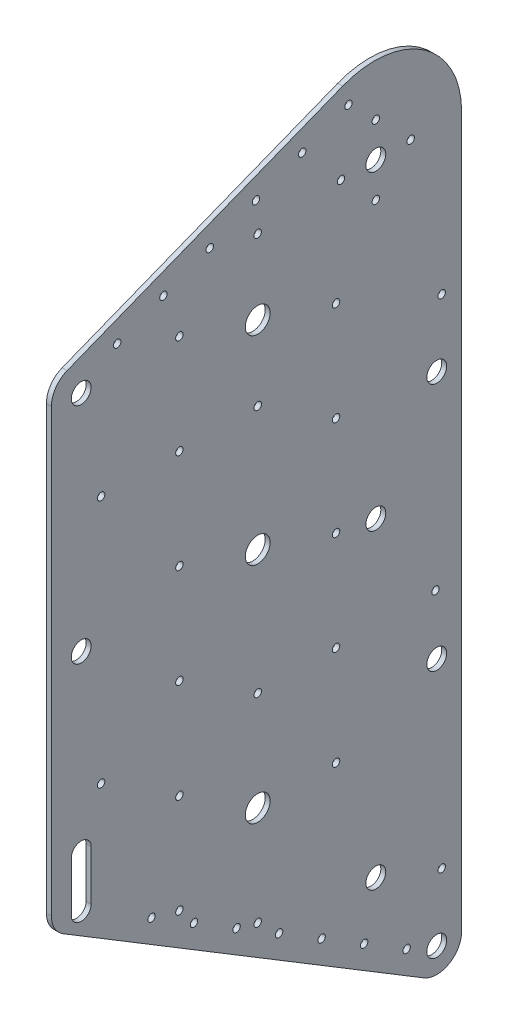
SolidWorks part; units mm, degrees
material "6061 Alloy"
ref_plane "Front Plane" through (0, 0, 0) normal (0, 0, 1) x (1, 0, 0)
ref_plane "Top Plane" through (0, 0, 0) normal (0, 1, 0) x (1, 0, 0)
ref_plane "Right Plane" through (0, 0, 0) normal (1, 0, 0) x (0, 0, -1)
sketch "Sketch2" plane through (0, 0, 0) normal (-1, 0, 0) x (0, 1, 0)
  line L0 (0, 0) -> (65, 165)
  line L1 (65, 165) -> (-290, 165)
  line L2 (-290, 165) -> (-190, 0)
  line L3 (-90.75, 0) -> (90.75, 0) construction
  line L4 (-190, 0) -> (0, 0)
  dimension "D1" = 355
  dimension "D2" = 190
  dimension "D3" = 165
  dimension "D4" = 65
extrude "Boss-Extrude1" add sketch "Sketch2" along normal blind 2
fillet "Fillet1" radius 10 3 edges at (-1, -190, 0) (-1, -290, -165) (-1, 0, 0)
sketch "Sketch3" plane through (-2, 0, 0) normal (-1, 0, 0) x (0, 1, 0)
  line L0 (-192.1703, 12) -> (-192.1703, 3.3924) construction
  line L1 (65, 165) -> (-272.2462, 165) construction
  line L2 (-280.7982, 149.817) -> (-192.9194, 4.817) construction
  line L3 (2.4955, 6.3348) -> (65, 165) construction
  line L4 (-164.1703, 12) -> (-164.1703, 3.3924) construction
  line L5 (-90.75, 0) -> (90.75, 0) construction
  line L6 (-261.9073, 134.0821) -> (-194.8085, 23.369) construction
  line L7 (-4.3733, 10.7251) -> (45.6685, 137.7543) construction
  line L8 (-102.1703, 12) -> (-102.1703, 4.9013) construction
  line L9 (-188.1703, 8) -> (-168.1703, 8)
  line L10 (-168.1703, 16) -> (-188.1703, 16)
  circle A0 centre (-272.2462, 155) radius 10 construction
  circle A1 centre (-228.1703, 83) radius 1.5
  circle A2 centre (-246.2462, 157) radius 1.5
  circle A3 centre (-46.2462, 157) radius 1.5
  circle A4 centre (11.8297, 83) radius 1.5
  circle A5 centre (13.8297, 130.5) radius 14 construction
  circle A6 centre (13.8297, 144.5) radius 1.5
  circle A7 centre (27.8297, 130.5) radius 1.5
  circle A8 centre (13.8297, 116.5) radius 1.5
  circle A9 centre (-0.1703, 130.5) radius 1.5
  arc A10 (-188.1703, 16) -> (-188.1703, 8) centre (-188.1703, 12) ccw
  arc A11 (-168.1703, 8) -> (-168.1703, 16) centre (-168.1703, 12) ccw
  circle A42 centre (-272.2462, 155) radius 4
  circle A43 centre (-172.2462, 155) radius 4
  circle A44 centre (13.8297, 130.5) radius 4
  circle A45 centre (-236.1703, 130.5) radius 4
  circle A46 centre (-111.1703, 130.5) radius 4
  circle A47 centre (-18.1703, 83) radius 5
  circle A48 centre (-188.1703, 83) radius 5
  circle A49 centre (-98.1703, 83) radius 5
  circle A50 centre (-205.05, 40.2675) radius 1.5
  circle A51 centre (-208.1703, 51.5) radius 1.5
  circle A52 centre (-225.7821, 74.4754) radius 1.5
  circle A53 centre (-236.1481, 91.5794) radius 1.5
  circle A54 centre (-246.5141, 108.6833) radius 1.5
  circle A55 centre (-256.8802, 125.7873) radius 1.5
  circle A56 centre (-267.2462, 142.8912) radius 1.5
  circle A57 centre (1.8297, 26.4713) radius 1.5
  circle A58 centre (9.1602, 45.0795) radius 1.5
  circle A59 centre (16.4907, 63.6876) radius 1.5
  circle A60 centre (23.8212, 82.2958) radius 1.5
  circle A61 centre (31.1517, 100.904) radius 1.5
  circle A62 centre (38.4822, 119.5121) radius 1.5
  circle A63 centre (-72.2462, 155) radius 4
  circle A64 centre (-148.1703, 154.5) radius 1.5
  circle A65 centre (-188.1703, 114.5) radius 1.5
  circle A66 centre (-148.1703, 114.5) radius 1.5
  circle A67 centre (-108.1703, 114.5) radius 1.5
  circle A68 centre (-68.1703, 114.5) radius 1.5
  circle A69 centre (-28.1703, 114.5) radius 1.5
  circle A70 centre (-148.1703, 83) radius 1.5
  circle A71 centre (-215.416, 57.3715) radius 1.5
  circle A72 centre (-168.1703, 51.5) radius 1.5
  circle A73 centre (-8.1703, 51.5) radius 1.5
  circle A74 centre (-128.1703, 51.5) radius 1.5
  circle A75 centre (-88.1703, 51.5) radius 1.5
  circle A76 centre (-48.1703, 83) radius 1.5
  circle A77 centre (-48.1703, 51.5) radius 1.5
  circle A78 centre (-8.1703, 12) radius 4
  circle A79 centre (-148.1703, 20) radius 1.5
  circle A80 centre (-98.1703, 12) radius 4
  circle A81 centre (-48.1703, 20) radius 1.5
  dimension "D1" = 3
  dimension "D2" = 8
  dimension "D3" = 20
  dimension "D4" = 20
  dimension "D6" = 20
  dimension "D7" = 20
  dimension "D8" = 20
  dimension "D9" = 8
  dimension "D10" = 5
  dimension "D11" = 20
  dimension "D12" = 12
  dimension "D13" = 31.5
  dimension "D14" = 31.5
  dimension "D15" = 31.5
  dimension "D16" = 40
  dimension "D17" = 40
  dimension "D18" = 40
  dimension "D19" = 40
  dimension "D20" = 40
  dimension "D21" = 40
  dimension "D22" = 12
  dimension "D24" = 40
  dimension "D25" = 90
  dimension "D26" = 80
  dimension "D27" = 50
  dimension "D28" = 10
  dimension "D29" = 40
  dimension "D30" = 40
  dimension "D31" = 40
  dimension "D32" = 40
  dimension "D33" = 3
  dimension "D34" = 16
  dimension "D35" = 125
  dimension "D37" = 8
  dimension "D38" = 10
  dimension "D39" = 20
  dimension "D40" = 20
  dimension "D41" = 20
  dimension "D42" = 20
  dimension "D43" = 20
  dimension "D44" = 100
  dimension "D45" = 100
  dimension "D46" = 40
  dimension "D47" = 30
  dimension "D48" = 8
  dimension "D5" = 20
  dimension "D23" = 90
  dimension "D36" = 125
  dimension "D49" = 26
  dimension "D50" = 200
  dimension "D51" = 3
  dimension "D52" = 28
  dimension "D53" = 28
  dimension "D54" = 62
extrude "Cut-Extrude1" cut sketch "Sketch3" against normal blind 2
fillet "Fillet2" radius 35 1 edges at (-1, 65, -165)
